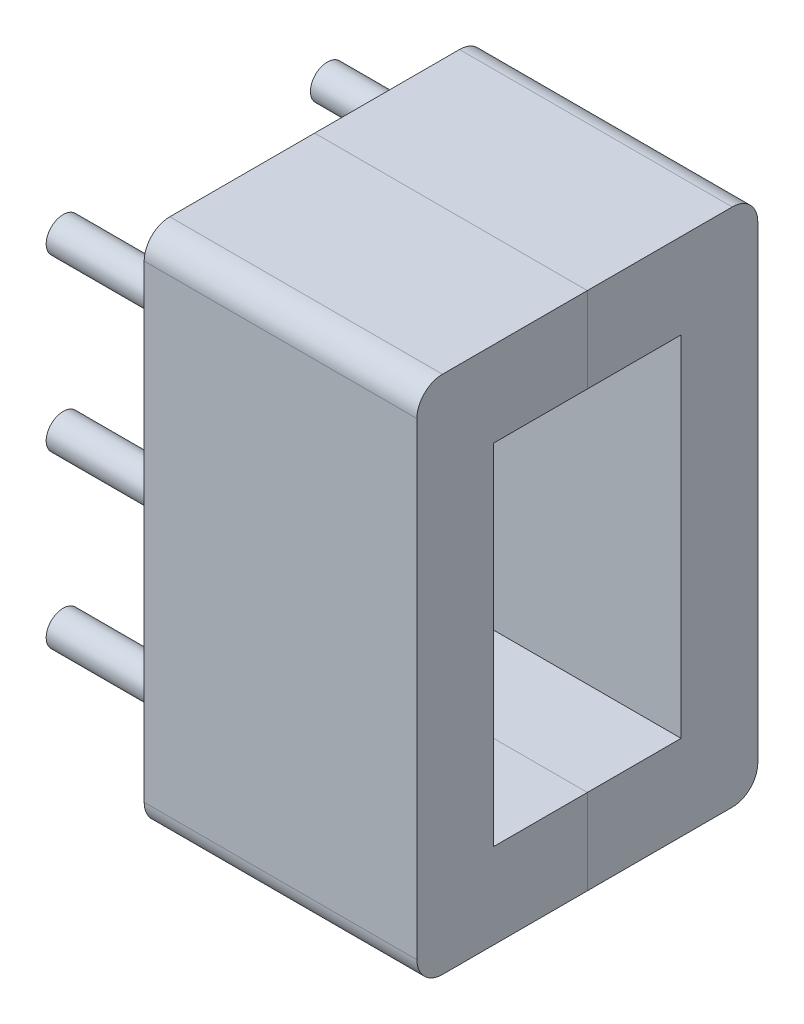
SolidWorks part; units mm, degrees
ref_plane "Alzado" through (0, 0, 0) normal (0, 0, 1) x (1, 0, 0)
ref_plane "Planta" through (0, 0, 0) normal (0, 1, 0) x (1, 0, 0)
ref_plane "Vista lateral" through (0, 0, 0) normal (1, 0, 0) x (0, 0, -1)
sketch "Croquis2" plane through (0, 0, 0) normal (1, 0, 0) x (0, 0, -1)
  line L0 (0, 24.489) -> (0, -53.3578) construction
  line L1 (5.835, 13.2874) -> (5.835, 12.9749) construction
  line L2 (10, 6.2874) -> (10, 3.7874) construction
  line L3 (5.835, -38.7126) -> (5.835, -38.4002) construction
  line L4 (5.835, -38.7126) -> (8, -38.7126) construction
  line L5 (9, -32.7126) -> (9, -37.7126) construction
  line L6 (10, -29.2126) -> (10, -31.7126) construction
  line L7 (5.835, 13.2874) -> (8, 13.2874) construction
  line L8 (9, 7.2874) -> (9, 12.2874) construction
  line L9 (6.5, 7.2874) -> (-6.5, 7.2874) construction
  line L10 (10, -29.2126) -> (10, 3.7874) construction
  line L11 (5.835, 13.2874) -> (5.835, 12.9749) construction
  line L12 (10, 6.2874) -> (10, 3.7874) construction
  line L13 (5.835, -38.7126) -> (5.835, -38.4002) construction
  line L14 (5.835, -38.7126) -> (8, -38.7126) construction
  line L15 (9, -32.7126) -> (9, -37.7126) construction
  line L16 (10, -29.2126) -> (10, -31.7126) construction
  line L17 (5.835, 13.2874) -> (8, 13.2874) construction
  line L18 (9, 7.2874) -> (9, 12.2874) construction
  line L19 (6.5, 7.2874) -> (-6.5, 7.2874) construction
  line L20 (10, -29.2126) -> (10, 3.7874) construction
  line L21 (-20, 17.7874) -> (20, 17.7874)
  line L22 (20, 17.7874) -> (20, -43.2126)
  line L24 (20, -43.2126) -> (-20, -43.2126)
  line L25 (-20, 17.7874) -> (-20, -43.2126)
  line L26 (-6.5, -32.7126) -> (6.5, -32.7126) construction
  line L27 (9, -32.7126) -> (6.5, -32.7126) construction
  line L28 (-6.5, -32.7126) -> (6.5, -32.7126) construction
  line L29 (9, -32.7126) -> (6.5, -32.7126) construction
  line L30 (-3, -33.7126) -> (-3, -32.7126) construction
  line L31 (3, -33.7126) -> (3, -32.7126) construction
  line L32 (-3, -33.7126) -> (-3, -32.7126) construction
  line L33 (3, -33.7126) -> (3, -32.7126) construction
  arc A0 (5.835, -38.4002) -> (4.335, -38.4002) centre (5.085, -36.3426) ccw construction
  arc A1 (4.335, 12.9749) -> (5.835, 12.9749) centre (5.085, 10.9174) ccw construction
  arc A2 (5.835, -38.4002) -> (4.335, -38.4002) centre (5.085, -36.3426) ccw construction
  arc A3 (4.335, 12.9749) -> (5.835, 12.9749) centre (5.085, 10.9174) ccw construction
  arc A4 (8, -38.7126) -> (9, -37.7126) centre (8, -37.7126) ccw construction
  arc A5 (9, -32.7126) -> (10, -31.7126) centre (9, -31.7126) ccw construction
  arc A6 (9, 12.2874) -> (8, 13.2874) centre (8, 12.2874) ccw construction
  arc A7 (10, 6.2874) -> (9, 7.2874) centre (9, 6.2874) ccw construction
  arc A8 (8, -38.7126) -> (9, -37.7126) centre (8, -37.7126) ccw construction
  arc A9 (9, -32.7126) -> (10, -31.7126) centre (9, -31.7126) ccw construction
  arc A10 (9, 12.2874) -> (8, 13.2874) centre (8, 12.2874) ccw construction
  arc A11 (10, 6.2874) -> (9, 7.2874) centre (9, 6.2874) ccw construction
  point P31 (0, -43.2126)
  point P33 (0, 17.7874)
  dimension "D1" = 4.5
  dimension "D2" = 10
  dimension "D3" = 4.5
extrude "Saliente-Extruir1" add sketch "Croquis2" against normal blind 32
sketch "Croquis4" plane through (0, 0, 0) normal (1, 0, 0) x (0, 0, -1)
  line L0 (3, -33.7126) -> (3, -32.7126) construction
  line L1 (-6.5, -32.7126) -> (6.5, -32.7126) construction
  line L2 (9, -32.7126) -> (6.5, -32.7126) construction
  line L3 (10, -29.2126) -> (10, -31.7126) construction
  line L4 (10, 6.2874) -> (10, 3.7874) construction
  line L5 (10, -29.2126) -> (10, 3.7874) construction
  line L6 (6.5, 7.2874) -> (-6.5, 7.2874) construction
  line L7 (0, 24.489) -> (0, -53.3578) construction
  line L8 (3, -33.7126) -> (3, -32.7126) construction
  line L9 (-6.5, -32.7126) -> (6.5, -32.7126) construction
  line L10 (9, -32.7126) -> (6.5, -32.7126) construction
  line L11 (10, -29.2126) -> (10, -31.7126) construction
  line L12 (10, 6.2874) -> (10, 3.7874) construction
  line L13 (10, -29.2126) -> (10, 3.7874) construction
  line L14 (6.5, 7.2874) -> (-6.5, 7.2874) construction
  line L15 (0, 24.489) -> (0, -53.3578) construction
  line L16 (-11, 7.7874) -> (11, 7.7874)
  line L17 (11, 7.7874) -> (11, -33.2126)
  line L19 (-11, 7.7874) -> (-11, -33.2126)
  line L35 (3, -33.7126) -> (2.5, -34.2126) construction
  line L43 (11, -33.2126) -> (-11, -33.2126)
  arc A0 (9, -32.7126) -> (10, -31.7126) centre (9, -31.7126) ccw construction
  arc A1 (9, -32.7126) -> (10, -31.7126) centre (9, -31.7126) ccw construction
  point P14 (0, -33.2126)
  point P20 (0, 7.7874)
  point P22 (0, -43.2126)
  dimension "D1" = 0.5
  dimension "D2" = 1
  dimension "D3" = 0.5
  dimension "D8" = 0.5
  dimension "D9" = 2.5
extrude "Cortar-Extruir1" cut sketch "Croquis4" against normal through all both and the other way through all
sketch "Croquis5" plane through (-32, 0, 0) normal (-1, 0, 0) x (0, 0, 1)
  line L0 (-9, 7.2874) -> (-9, 12.2874) construction
  line L1 (-9, -32.7126) -> (-9, -37.7126) construction
  line L2 (-5.835, -38.7126) -> (-8, -38.7126) construction
  line L3 (-5.835, 13.2874) -> (-8, 13.2874) construction
  line L4 (-9, 7.2874) -> (-9, 12.2874) construction
  line L5 (-9, -32.7126) -> (-9, -37.7126) construction
  line L6 (-5.835, -38.7126) -> (-8, -38.7126) construction
  line L7 (-5.835, 13.2874) -> (-8, 13.2874) construction
  line L8 (0, 24.489) -> (0, -53.3578) construction
  line L9 (0, 24.489) -> (0, -53.3578) construction
  line L10 (9.25, 13.5374) -> (-9.25, 13.5374)
  line L11 (-9.25, 13.5374) -> (-9.25, -38.9626)
  line L12 (-9.25, -38.9626) -> (9.25, -38.9626)
  line L13 (9.25, 13.5374) -> (9.25, -38.9626)
  arc A0 (-4.335, -38.4002) -> (-5.835, -38.4002) centre (-5.085, -36.3426) ccw construction
  arc A1 (-5.835, 12.9749) -> (-4.335, 12.9749) centre (-5.085, 10.9174) ccw construction
  arc A2 (-4.335, -38.4002) -> (-5.835, -38.4002) centre (-5.085, -36.3426) ccw construction
  arc A3 (-5.835, 12.9749) -> (-4.335, 12.9749) centre (-5.085, 10.9174) ccw construction
  point P21 (0, -38.9626)
  point P22 (0, 13.5374)
  dimension "D1" = 0.25
  dimension "D2" = 0.25
  dimension "D3" = 0.25
extrude "Cortar-Extruir2" cut sketch "Croquis5" against normal blind 8 and the other way through all
sketch "Croquis7" plane through (-24, 0, 0) normal (-1, 0, 0) x (0, 0, 1)
  line L4 (-9.25, 7.7874) -> (9.25, 7.7874)
  line L5 (9.25, 7.7874) -> (9.25, 13.5374)
  line L6 (9.25, 13.5374) -> (-9.25, 13.5374)
  line L7 (-9.25, 13.5374) -> (-9.25, 7.7874)
  line L8 (-9.25, 7.7874) -> (9.25, 7.7874)
  line L9 (9.25, 7.7874) -> (9.25, 13.5374)
  line L10 (9.25, 13.5374) -> (-9.25, 13.5374)
  line L11 (-9.25, 13.5374) -> (-9.25, 7.7874)
  line L12 (9.25, -33.2126) -> (-9.25, -33.2126)
  line L13 (-9.25, -33.2126) -> (-9.25, -38.9626)
  line L14 (-9.25, -38.9626) -> (9.25, -38.9626)
  line L15 (9.25, -38.9626) -> (9.25, -33.2126)
  line L16 (9.25, -33.2126) -> (-9.25, -33.2126)
  line L17 (-9.25, -33.2126) -> (-9.25, -38.9626)
  line L18 (-9.25, -38.9626) -> (9.25, -38.9626)
  line L19 (9.25, -38.9626) -> (9.25, -33.2126)
  dimension "D1" = 0
  dimension "D2" = 0
extrude "Saliente-Extruir2" add sketch "Croquis7" along normal up to surface (8 mm away) from offset 1.25 up to face at (-32, -12.7126, 0)
sketch "Croquis9" plane through (-32, 0, 0) normal (1, 0, 0) x (0, 0, -1)
  line L0 (-15.5, 3.7699) -> (-15.5, -40.0796) construction
  line L2 (100, 3.7699) -> (-100, 3.7699) construction
  line L3 (100, 12.7699) -> (-100, 12.7699) construction
  line L4 (-20, 17.7874) -> (-20, -43.2126) construction
  line L5 (-11, -33.2126) -> (-11, 7.7874) construction
  line L6 (-20, 17.7874) -> (-20, -43.2126) construction
  line L7 (-11, -33.2126) -> (-11, 7.7874) construction
  line L8 (0, 24.489) -> (0, -53.3578) construction
  line L9 (0, 24.489) -> (0, -53.3578) construction
  line L10 (-20, 6.2236) -> (-11, 6.2236) construction
  line L11 (-15.5, 3.7699) -> (-15.5, 12.7699) construction
  circle A0 centre (-15.5, 8.2699) radius 2
  circle A1 centre (-15.5, -31.7301) radius 2
  circle A2 centre (-15.5, -11.7301) radius 2
  circle A3 centre (15.5, -31.7301) radius 2
  circle A4 centre (15.5, -11.7301) radius 2
  circle A5 centre (15.5, 8.2699) radius 2
  point P14 (-15.5, 6.2236)
  point P22 (0, 0)
  dimension "D1" = 40
  dimension "D2" = 20
  dimension "D3" = 4
extrude "Saliente-Extruir3" add sketch "Croquis9" against normal blind 14
fillet "Redondeo1" radius 3 4 edges at (-16, -43.2126, 20) (-16, -43.2126, -20) (-16, 17.7874, -20) (-16, 17.7874, 20)
sketch "Croquis10" plane through (0, 0, 20) normal (0, 0, 1) x (1, 0, 0)
  line L0 (0, 14.7874) -> (-32, 14.7874) construction
  line L1 (0, 14.7874) -> (-32, 14.7874) construction
split "Partir1" trim tools "Alzado" bodies to split 108 resulting bodies 106 107
